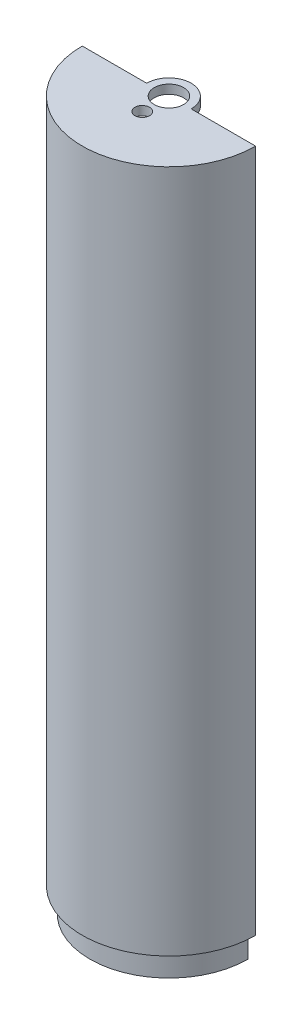
SolidWorks part; units mm, degrees
ref_plane "Front Plane" through (0, 0, 0) normal (0, 0, 1) x (1, 0, 0)
ref_plane "Top Plane" through (0, 0, 0) normal (0, 1, 0) x (1, 0, 0)
ref_plane "Right Plane" through (0, 0, 0) normal (1, 0, 0) x (0, 0, -1)
sketch "Sketch1" plane through (0, 0, 0) normal (0, 1, 0) x (1, 0, 0)
  circle A0 centre (0, 0) radius 49.4538
  dimension "D1" = 98.9076
extrude "Boss-Extrude1" add sketch "Sketch1" along normal blind 3.81 and the other way blind 6.35
sketch "Sketch2" plane through (0, 3.81, 0) normal (0, 1, 0) x (1, 0, 0)
  circle A0 centre (0, 0) radius 49.4538
  dimension "D1" = 98.9076
extrude "Boss-Extrude2" add sketch "Sketch2" along normal blind 381
shell "Shell1" thickness 3.175 removed face at (0, 384.81, 49.4538)
sketch "Sketch4" plane through (0, -6.35, 0) normal (0, -1, 0) x (1, 0, 0)
  line L0 (49.4538, 0) -> (12.7, 0)
  line L1 (-12.7, 0) -> (-49.4538, 0)
  circle A0 centre (0, 0) radius 49.4538 construction
  arc A1 (-12.7, 0) -> (12.7, 0) centre (0, 0) ccw
  arc A2 (-49.4538, 0) -> (49.4538, 0) centre (0, 0) ccw
  dimension "D1" = 25.4
extrude "Cut-Extrude1" cut sketch "Sketch4" against normal through all contours A2 L0 A1 L1
sketch "Sketch5" plane through (0, -3.175, 0) normal (0, 1, 0) x (1, 0, 0)
  line L0 (-46.2788, 0) -> (-12.7, 0)
  line L1 (12.7, 0) -> (46.2788, 0)
  arc A0 (-46.2788, 0) -> (46.2788, 0) centre (0, 0) ccw
  arc A1 (12.7, 0) -> (-12.7, 0) centre (0, 0) ccw
  dimension "D1" = 25.4
extrude "Boss-Extrude3" add sketch "Sketch5" along normal blind 3.81
sketch "Sketch7" plane through (0, -6.35, 0) normal (0, -1, 0) x (1, 0, 0)
  circle A0 centre (0, 0) radius 49.4538
  circle A1 centre (0, 0) radius 45.085
  dimension "D1" = 98.9076
  dimension "D2" = 90.17
extrude "Cut-Extrude2" cut sketch "Sketch7" against normal blind 6.35
sketch "Sketch9" plane through (0, -6.35, 0) normal (0, -1, 0) x (1, 0, 0)
  line L0 (45.085, 0) -> (12.7, 0)
  line L1 (-12.7, 0) -> (-45.085, 0)
  arc A0 (45.085, 0) -> (-45.085, 0) centre (0, 0) ccw
  arc A1 (-12.7, 0) -> (12.7, 0) centre (0, 0) ccw
  dimension "D2" = 25.4
extrude "Boss-Extrude4" add sketch "Sketch9" along normal blind 7.62 contours A0 L1 A1 L0
sketch "Sketch10" plane through (0, 0.635, 0) normal (0, 1, 0) x (1, 0, 0)
  circle A2 centre (0, 0) radius 16.51
  circle A3 centre (0, 0) radius 35.56
  dimension "D1" = 33.02
  dimension "D2" = 71.12
extrude "Cut-Extrude3" cut sketch "Sketch10" against normal blind 6.35 contours A3
sketch "Sketch11" plane through (0, -5.715, 0) normal (0, 1, 0) x (1, 0, 0)
  circle A0 centre (0, 0) radius 8.382
  dimension "D1" = 16.764
extrude "Cut-Extrude4" cut sketch "Sketch11" against normal blind 5.08
sketch "Sketch12" plane through (0, -10.795, 0) normal (0, 1, 0) x (1, 0, 0)
  circle A0 centre (0, 0) radius 3.302
  dimension "D1" = 6.604
extrude "Cut-Extrude5" cut sketch "Sketch12" against normal through all
sketch "Sketch13" plane through (0, 0.635, 0) normal (0, 1, 0) x (1, 0, 0)
  line L0 (-46.2788, 0) -> (-35.56, 0)
  line L1 (35.56, 0) -> (46.2788, 0)
  arc A0 (-46.2788, 0) -> (46.2788, 0) centre (0, 0) ccw
  arc A1 (-35.56, 0) -> (35.56, 0) centre (0, 0) ccw
extrude "Boss-Extrude5" add sketch "Sketch13" along normal blind 5.08
sketch "Sketch14" plane through (0, -13.97, 0) normal (0, -1, 0) x (1, 0, 0)
  circle A0 centre (0, 15.24) radius 4.191
  dimension "D1" = 8.382
  dimension "D2" = 15.24
extrude "Cut-Extrude6" cut sketch "Sketch14" against normal through all
sketch "Sketch15" plane through (0, 384.81, 0) normal (0, 1, 0) x (1, 0, 0)
  line L0 (46.2788, 0) -> (35.56, 0) construction
  line L1 (35.56, 0) -> (12.7, 0) construction
  line L2 (-35.56, 0) -> (-46.2788, 0) construction
  line L3 (-12.7, 0) -> (-35.56, 0) construction
  line L4 (46.2788, 0) -> (35.56, 0)
  line L5 (35.56, 0) -> (12.7, 0)
  line L6 (-35.56, 0) -> (-46.2788, 0)
  line L7 (-12.7, 0) -> (-35.56, 0)
  line L8 (49.4538, 0) -> (46.2788, 0) construction
  line L9 (-46.2788, 0) -> (-49.4538, 0) construction
  line L10 (49.4538, 0) -> (46.2788, 0)
  line L11 (-46.2788, 0) -> (-49.4538, 0)
  arc A0 (12.7, 0) -> (-12.7, 0) centre (0, 0) ccw construction
  arc A1 (12.7, 0) -> (-12.7, 0) centre (0, 0) ccw
  arc A2 (-49.4538, 0) -> (49.4538, 0) centre (0, 0) ccw construction
  arc A3 (-49.4538, 0) -> (49.4538, 0) centre (0, 0) ccw
extrude "Boss-Extrude6" add sketch "Sketch15" along normal blind 5.08
sketch "Sketch16" plane through (0, 384.81, 0) normal (0, -1, 0) x (1, 0, 0)
  circle A2 centre (0, 0) radius 8.382 construction
  circle A3 centre (0, 0) radius 8.382
extrude "Cut-Extrude7" cut sketch "Sketch16" against normal through all
sketch "Sketch17" plane through (0, 389.89, 0) normal (0, 1, 0) x (1, 0, 0)
  circle A0 centre (0, -15.24) radius 4.191 construction
  circle A2 centre (0, -15.24) radius 4.191
extrude "Cut-Extrude8" cut sketch "Sketch17" against normal up to next
